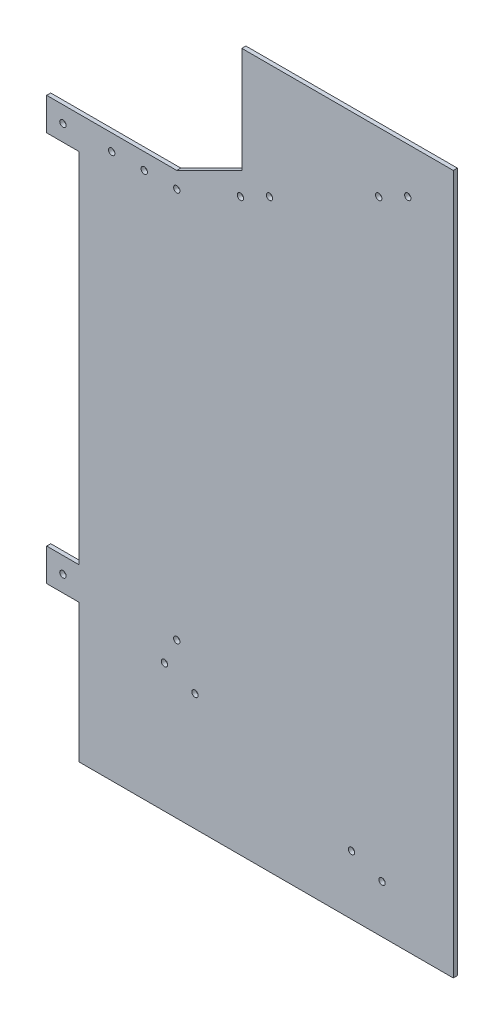
SolidWorks part; units mm, degrees
ref_plane "Front Plane" through (0, 0, 0) normal (1, 0, 0) x (0, 1, 0)
ref_plane "Top Plane" through (0, 0, 0) normal (0, 0, 1) x (0, 1, 0)
ref_plane "Right Plane" through (0, 0, 0) normal (0, 1, 0) x (-1, 0, 0)
sketch "Sketch1" plane through (0, 0, 0) normal (0, 0, 1) x (0, 1, 0)
  line L0 (-330.2, -25.4) -> (-330.2, 0)
  line L1 (-330.2, 0) -> (0, 0) construction
  line L2 (0, 0) -> (0, -101.6)
  line L3 (-330.2, -25.4) -> (-438.15, -317.5) construction
  line L4 (-438.15, -317.5) -> (107.95, -317.5)
  line L5 (25.4, -152.4) -> (0, -101.6)
  line L6 (-330.2, -25.4) -> (-438.15, -25.4)
  line L7 (-438.15, -25.4) -> (-438.15, -317.5)
  line L8 (25.4, -152.4) -> (107.95, -152.4)
  line L9 (107.95, -152.4) -> (107.95, -317.5)
  line L10 (0, -101.6) -> (107.95, -317.5) construction
  line L11 (-304.8, 0) -> (-304.8, -25.4)
  line L12 (-304.8, -25.4) -> (-25.4, -25.4)
  line L13 (-25.4, -25.4) -> (-25.4, 0)
  line L14 (-330.2, 0) -> (-304.8, 0)
  line L15 (-25.4, 0) -> (0, 0)
  point P2 (-165.1, -317.5)
  point P7 (-165.1, 0)
  dimension "D1" = 330.2
  dimension "D2" = 25.4
  dimension "D3" = 546.1
  dimension "D4" = 292.1
  dimension "D5" = 101.6
  dimension "D6" = 50.8
  dimension "D7" = 25.4
  dimension "D8" = 25.4
extrude "Boss-Extrude1" add sketch "Sketch1" along normal blind 3.175
sketch "Sketch2" plane through (0, 0, 0) normal (0, 0, -1) x (1, 0, 0)
  line L1 (0, 330.2) -> (25.4, 330.2) construction
  line L2 (101.6, 0) -> (0, 0) construction
  line L3 (0, 304.8) -> (0, 330.2) construction
  line L9 (25.4, 25.4) -> (25.4, 304.8) construction
  point P0 (12.7, 317.5)
  point P1 (12.7, 12.7)
  point P15 (101.6, 317.5)
  point P17 (101.6, 12.7)
  point P20 (50.8, 12.7)
  point P22 (76.2, 12.7)
  point P37 (0, 0)
  dimension "D1" = 12.7
  dimension "D2" = 12.7
  dimension "D3" = 12.7
  dimension "D4" = 88.9
  dimension "D5" = 25.4
  dimension "D6" = 25.4
hole_wizard "#9 (0.196) Diameter Hole1" positions "Sketch2" profile "Sketch3" hole size "#9" standard "ANSI Inch" end condition through all
sketch "Sketch3" plane through (12.7, -317.5, 0) normal (1, 0, 0) x (0, 1, 0)
  line L0 (0, 0) -> (0, 3.175)
  line L1 (0, 3.175) -> (2.4892, 3.175)
  line L2 (2.4892, 3.175) -> (2.4892, 0)
  line L5 (2.4892, 0) -> (0, 0)
  line L11 (0, -6.35) -> (0, 107.95) construction
  dimension "Thru Hole Dia." = 4.9784
  dimension "Thru Hole Depth" = 3.175
sketch "Sketch5" plane through (0, 0, 3.175) normal (0, 0, 1) x (1, 0, 0)
  line L0 (108.6995, -14.199) -> (324.5995, 93.751) construction
  line L1 (317.5, -438.15) -> (317.5, 107.95) construction
  line L2 (30.9031, -315.3093) -> (323.0031, -423.2593) construction
  line L4 (152.4, 25.4) -> (101.6, 0) construction
  line L5 (108.6995, -14.199) -> (151.3153, 7.1089) construction
  line L6 (174.0337, 18.4681) -> (216.6495, 39.776) construction
  line L7 (216.6495, 39.776) -> (259.2653, 61.0839) construction
  line L8 (281.9837, 72.4431) -> (324.5995, 93.751) construction
  line L9 (30.9031, -315.3093) -> (92.0155, -337.8944) construction
  line L10 (115.8406, -346.6993) -> (176.9531, -369.2843) construction
  line L11 (176.9531, -369.2843) -> (238.0655, -391.8694) construction
  line L12 (261.8906, -400.6743) -> (323.0031, -423.2593) construction
  line L14 (101.6, 0) -> (108.6995, -14.199) construction
  line L16 (317.5, 107.95) -> (324.5995, 93.751) construction
  line L18 (25.4, -330.2) -> (30.9031, -315.3093) construction
  line L20 (323.0031, -423.2593) -> (317.5, -438.15) construction
  point P12 (174.0337, 18.4681)
  point P14 (151.3153, 7.1089)
  point P15 (259.2653, 61.0839)
  point P16 (281.9837, 72.4431)
  point P17 (92.0155, -337.8944)
  point P18 (115.8406, -346.6993)
  point P19 (238.0655, -391.8694)
  point P20 (261.8906, -400.6743)
  point P53 (0, 0)
  point P55 (0, 0)
  dimension "D1" = 15.875
  dimension "D2" = 15.875
  dimension "D3" = 25.4
  dimension "D4" = 25.4
  dimension "D5" = 25.4
  dimension "D6" = 25.4
hole_wizard "#9 (0.196) Diameter Hole2" positions "Sketch5" profile "Sketch6" hole size "#9" standard "ANSI Inch" end condition through all
sketch "Sketch6" plane through (261.8906, -400.6743, 3.175) normal (1, 0, 0) x (0, -1, 0)
  line L0 (0, 0) -> (0, 3.175)
  line L1 (0, 3.175) -> (2.4892, 3.175)
  line L2 (2.4892, 3.175) -> (2.4892, 0)
  line L5 (2.4892, 0) -> (0, 0)
  line L11 (0, -6.35) -> (0, 107.95) construction
  dimension "Thru Hole Dia." = 4.9784
  dimension "Thru Hole Depth" = 3.175
